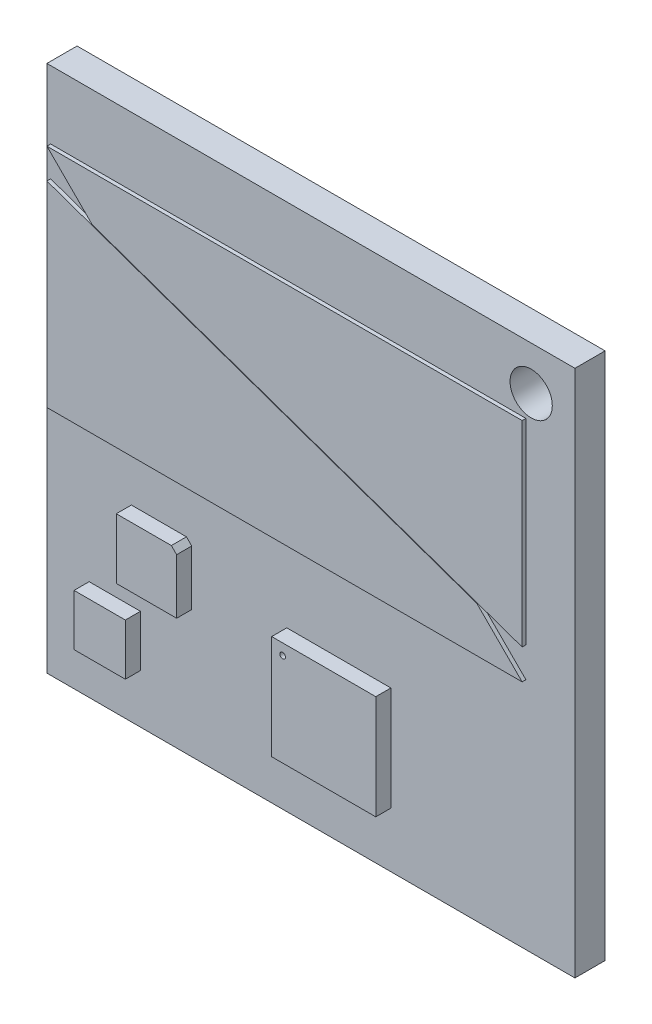
SolidWorks part; units mm, degrees
ref_plane "Front Plane" through (0, 0, 0) normal (0, 0, 1) x (1, 0, 0)
ref_plane "Top Plane" through (0, 0, 0) normal (0, 1, 0) x (1, 0, 0)
ref_plane "Right Plane" through (0, 0, 0) normal (1, 0, 0) x (0, 0, -1)
sketch "Model" plane through (0, 0, 0) normal (0, 0, 1) x (1, 0, 0)
  line L0 (0, 0) -> (35, 0)
  line L1 (35, 0) -> (35, 35)
  line L2 (35, 35) -> (0, 35)
  line L3 (0, 35) -> (0, 0)
  line L4 (22.2, 2.2195) -> (22.2, 2.2805)
  line L5 (18.85, 12.0305) -> (18.85, 11.9695)
  line L6 (24.7805, 2) -> (24.7195, 2)
  line L7 (26.5805, 2) -> (26.5195, 2)
  line L8 (10.7805, 8.85) -> (10.7195, 8.85)
  line L9 (3.9305, 9.25) -> (3.8695, 9.25)
  line L10 (2.6305, 10.35) -> (2.5695, 10.35)
  line L11 (9.35, 4.1305) -> (9.35, 4.0695)
  line L12 (1.8805, 2.7) -> (1.8195, 2.7)
  line L13 (9.9, 1.7305) -> (9.9, 1.6695)
  line L14 (16.47, 0.59) -> (16.47, 1.05)
  line L15 (16.47, 1.51) -> (16.47, 1.05)
  line L16 (16.47, 1.05) -> (16.16, 0.8162)
  line L17 (16.4546, 1.0754) -> (16.16, 1.2684)
  line L18 (29.715, 12.57) -> (30.985, 12.57)
  line L19 (30.985, 12.57) -> (31.62, 11.935)
  line L20 (31.62, 10.665) -> (30.985, 10.03)
  line L21 (31.62, 11.935) -> (32.255, 12.57)
  line L22 (32.255, 12.57) -> (33.525, 12.57)
  line L23 (33.525, 12.57) -> (34.16, 11.935)
  line L24 (34.16, 10.665) -> (33.525, 10.03)
  line L25 (33.525, 10.03) -> (32.255, 10.03)
  line L26 (32.255, 10.03) -> (31.62, 10.665)
  line L27 (29.08, 11.935) -> (29.08, 10.665)
  line L28 (29.715, 12.57) -> (29.08, 11.935)
  line L29 (29.08, 10.665) -> (29.715, 10.03)
  line L30 (30.985, 10.03) -> (29.715, 10.03)
  line L31 (34.16, 11.935) -> (34.16, 10.665)
  line L32 (29.715, 10.02) -> (30.985, 10.02)
  line L33 (30.985, 10.02) -> (31.62, 9.385)
  line L34 (31.62, 8.115) -> (30.985, 7.48)
  line L35 (31.62, 9.385) -> (32.255, 10.02)
  line L36 (32.255, 10.02) -> (33.525, 10.02)
  line L37 (33.525, 10.02) -> (34.16, 9.385)
  line L38 (34.16, 8.115) -> (33.525, 7.48)
  line L39 (33.525, 7.48) -> (32.255, 7.48)
  line L40 (32.255, 7.48) -> (31.62, 8.115)
  line L41 (29.08, 9.385) -> (29.08, 8.115)
  line L42 (29.715, 10.02) -> (29.08, 9.385)
  line L43 (29.08, 8.115) -> (29.715, 7.48)
  line L44 (30.985, 7.48) -> (29.715, 7.48)
  line L45 (34.16, 9.385) -> (34.16, 8.115)
  line L46 (0.25, 15.5) -> (0.25, 28.5)
  line L47 (0.25, 28.5) -> (28.75, 18.5)
  line L48 (0.25, 15.5) -> (31.75, 15.5)
  line L49 (28.75, 18.5) -> (31.75, 15.5)
  line L50 (0.25, 30.5) -> (31.75, 30.5)
  line L51 (31.75, 30.5) -> (31.75, 17.5)
  line L52 (3.25, 27.5) -> (31.75, 17.5)
  line L53 (0.25, 30.5) -> (3.25, 27.5)
  line L54 (15.9, 10.55) -> (22.8, 10.55)
  line L55 (15.9, 10.55) -> (15.9, 3.65)
  line L56 (15.9, 3.65) -> (22.8, 3.65)
  line L57 (22.8, 3.65) -> (22.8, 10.55)
  line L58 (2.8, 6.65) -> (3.4, 6.65)
  line L59 (2.8, 6.65) -> (2.8, 6.05)
  line L60 (2.8, 3.85) -> (2.8, 3.25)
  line L61 (2.8, 3.25) -> (3.4, 3.25)
  line L62 (5.6, 3.25) -> (6.2, 3.25)
  line L63 (6.2, 3.25) -> (6.2, 3.85)
  line L64 (6.135, 6.23) -> (5.76, 6.585)
  line L65 (5.6, 8.8) -> (5.6, 8.45)
  line L66 (5.95, 8.45) -> (5.6, 8.45)
  line L67 (5.6, 12.1) -> (5.6, 12.45)
  line L68 (5.6, 12.45) -> (5.95, 12.45)
  line L69 (9.25, 8.45) -> (9.6, 8.45)
  line L70 (9.6, 8.45) -> (9.6, 8.8)
  line L71 (9.6, 12.1) -> (9.25, 12.45)
  line L72 (18.05, 2.45) -> (18.45, 2.45)
  line L73 (18.45, 2.45) -> (20.05, 2.45)
  line L74 (20.05, 2.45) -> (20.05, 0.85)
  line L75 (20.05, 0.85) -> (18.05, 0.85)
  line L76 (18.05, 0.85) -> (18.05, 2.05)
  line L77 (18.05, 2.05) -> (18.05, 2.45)
  line L78 (18.05, 2.05) -> (18.45, 2.45)
  line L79 (2.8, 3.25) -> (2.8, 6.65)
  line L80 (2.8, 3.25) -> (6.2, 3.25)
  line L81 (2.8, 6.65) -> (6.2, 6.65)
  line L82 (6.2, 3.25) -> (6.2, 6.65)
  line L83 (9.6, 8.45) -> (5.6, 8.45)
  line L84 (9.6, 8.45) -> (9.6, 12.45)
  line L85 (5.6, 8.45) -> (5.6, 12.45)
  line L86 (9.6, 12.45) -> (5.6, 12.45)
  circle A0 centre (32.1, 32.1) radius 1.4
  arc A1 (22.3397, 2.2805) -> (22.0603, 2.2805) centre (22.2, 2.2805) ccw
  arc A2 (22.0603, 2.2195) -> (22.3397, 2.2195) centre (22.2, 2.2195) ccw
  arc A3 (18.7103, 11.9695) -> (18.9897, 11.9695) centre (18.85, 11.9695) ccw
  arc A4 (18.9897, 12.0305) -> (18.7103, 12.0305) centre (18.85, 12.0305) ccw
  arc A5 (24.7195, 2.1397) -> (24.7195, 1.8603) centre (24.7195, 2) ccw
  arc A6 (24.7805, 1.8603) -> (24.7805, 2.1397) centre (24.7805, 2) ccw
  arc A7 (26.5195, 2.1397) -> (26.5195, 1.8603) centre (26.5195, 2) ccw
  arc A8 (26.5805, 1.8603) -> (26.5805, 2.1397) centre (26.5805, 2) ccw
  arc A9 (10.7195, 8.9897) -> (10.7195, 8.7103) centre (10.7195, 8.85) ccw
  arc A10 (10.7805, 8.7103) -> (10.7805, 8.9897) centre (10.7805, 8.85) ccw
  arc A11 (3.8695, 9.3897) -> (3.8695, 9.1103) centre (3.8695, 9.25) ccw
  arc A12 (3.9305, 9.1103) -> (3.9305, 9.3897) centre (3.9305, 9.25) ccw
  arc A13 (2.5695, 10.4897) -> (2.5695, 10.2103) centre (2.5695, 10.35) ccw
  arc A14 (2.6305, 10.2103) -> (2.6305, 10.4897) centre (2.6305, 10.35) ccw
  arc A15 (9.2103, 4.0695) -> (9.4897, 4.0695) centre (9.35, 4.0695) ccw
  arc A16 (9.4897, 4.1305) -> (9.2103, 4.1305) centre (9.35, 4.1305) ccw
  arc A17 (1.8195, 2.8397) -> (1.8195, 2.5603) centre (1.8195, 2.7) ccw
  arc A18 (1.8805, 2.5603) -> (1.8805, 2.8397) centre (1.8805, 2.7) ccw
  arc A19 (9.7603, 1.6695) -> (10.0397, 1.6695) centre (9.9, 1.6695) ccw
  arc A20 (10.0397, 1.7305) -> (9.7603, 1.7305) centre (9.9, 1.7305) ccw
  arc A21 (16.5208, 1.05) -> (16.4192, 1.05) centre (16.47, 1.05) ccw
  arc A22 (16.4192, 0.59) -> (16.5208, 0.59) centre (16.47, 0.59) ccw
  arc A23 (16.4192, 1.05) -> (16.5208, 1.05) centre (16.47, 1.05) ccw
  arc A24 (16.5208, 1.51) -> (16.4192, 1.51) centre (16.47, 1.51) ccw
  arc A25 (16.1294, 0.8568) -> (16.1906, 0.7756) centre (16.16, 0.8162) ccw
  arc A26 (16.5006, 1.0094) -> (16.4394, 1.0906) centre (16.47, 1.05) ccw
  arc A27 (16.1878, 1.3109) -> (16.1322, 1.2259) centre (16.16, 1.2684) ccw
  arc A28 (16.4268, 1.0329) -> (16.4824, 1.1179) centre (16.4546, 1.0754) ccw
  arc A29 (30.985, 12.5192) -> (30.985, 12.6208) centre (30.985, 12.57) ccw
  arc A30 (29.715, 12.6208) -> (29.715, 12.5192) centre (29.715, 12.57) ccw
  arc A31 (31.5841, 11.8991) -> (31.6559, 11.9709) centre (31.62, 11.935) ccw
  arc A32 (31.0209, 12.6059) -> (30.9491, 12.5341) centre (30.985, 12.57) ccw
  arc A33 (30.9491, 10.0659) -> (31.0209, 9.9941) centre (30.985, 10.03) ccw
  arc A34 (31.6559, 10.6291) -> (31.5841, 10.7009) centre (31.62, 10.665) ccw
  arc A35 (32.2909, 12.5341) -> (32.2191, 12.6059) centre (32.255, 12.57) ccw
  arc A36 (31.5841, 11.9709) -> (31.6559, 11.8991) centre (31.62, 11.935) ccw
  arc A37 (33.525, 12.5192) -> (33.525, 12.6208) centre (33.525, 12.57) ccw
  arc A38 (32.255, 12.6208) -> (32.255, 12.5192) centre (32.255, 12.57) ccw
  arc A39 (34.1241, 11.8991) -> (34.1959, 11.9709) centre (34.16, 11.935) ccw
  arc A40 (33.5609, 12.6059) -> (33.4891, 12.5341) centre (33.525, 12.57) ccw
  arc A41 (33.4891, 10.0659) -> (33.5609, 9.9941) centre (33.525, 10.03) ccw
  arc A42 (34.1959, 10.6291) -> (34.1241, 10.7009) centre (34.16, 10.665) ccw
  arc A43 (32.255, 10.0808) -> (32.255, 9.9792) centre (32.255, 10.03) ccw
  arc A44 (33.525, 9.9792) -> (33.525, 10.0808) centre (33.525, 10.03) ccw
  arc A45 (31.6559, 10.7009) -> (31.5841, 10.6291) centre (31.62, 10.665) ccw
  arc A46 (32.2191, 9.9941) -> (32.2909, 10.0659) centre (32.255, 10.03) ccw
  arc A47 (29.0292, 10.665) -> (29.1308, 10.665) centre (29.08, 10.665) ccw
  arc A48 (29.1308, 11.935) -> (29.0292, 11.935) centre (29.08, 11.935) ccw
  arc A49 (29.0441, 11.9709) -> (29.1159, 11.8991) centre (29.08, 11.935) ccw
  arc A50 (29.7509, 12.5341) -> (29.6791, 12.6059) centre (29.715, 12.57) ccw
  arc A51 (29.6791, 9.9941) -> (29.7509, 10.0659) centre (29.715, 10.03) ccw
  arc A52 (29.1159, 10.7009) -> (29.0441, 10.6291) centre (29.08, 10.665) ccw
  arc A53 (29.715, 10.0808) -> (29.715, 9.9792) centre (29.715, 10.03) ccw
  arc A54 (30.985, 9.9792) -> (30.985, 10.0808) centre (30.985, 10.03) ccw
  arc A55 (34.1092, 10.665) -> (34.2108, 10.665) centre (34.16, 10.665) ccw
  arc A56 (34.2108, 11.935) -> (34.1092, 11.935) centre (34.16, 11.935) ccw
  arc A57 (30.985, 9.9692) -> (30.985, 10.0708) centre (30.985, 10.02) ccw
  arc A58 (29.715, 10.0708) -> (29.715, 9.9692) centre (29.715, 10.02) ccw
  arc A59 (31.5841, 9.3491) -> (31.6559, 9.4209) centre (31.62, 9.385) ccw
  arc A60 (31.0209, 10.0559) -> (30.9491, 9.9841) centre (30.985, 10.02) ccw
  arc A61 (30.9491, 7.5159) -> (31.0209, 7.4441) centre (30.985, 7.48) ccw
  arc A62 (31.6559, 8.0791) -> (31.5841, 8.1509) centre (31.62, 8.115) ccw
  arc A63 (32.2909, 9.9841) -> (32.2191, 10.0559) centre (32.255, 10.02) ccw
  arc A64 (31.5841, 9.4209) -> (31.6559, 9.3491) centre (31.62, 9.385) ccw
  arc A65 (33.525, 9.9692) -> (33.525, 10.0708) centre (33.525, 10.02) ccw
  arc A66 (32.255, 10.0708) -> (32.255, 9.9692) centre (32.255, 10.02) ccw
  arc A67 (34.1241, 9.3491) -> (34.1959, 9.4209) centre (34.16, 9.385) ccw
  arc A68 (33.5609, 10.0559) -> (33.4891, 9.9841) centre (33.525, 10.02) ccw
  arc A69 (33.4891, 7.5159) -> (33.5609, 7.4441) centre (33.525, 7.48) ccw
  arc A70 (34.1959, 8.0791) -> (34.1241, 8.1509) centre (34.16, 8.115) ccw
  arc A71 (32.255, 7.5308) -> (32.255, 7.4292) centre (32.255, 7.48) ccw
  arc A72 (33.525, 7.4292) -> (33.525, 7.5308) centre (33.525, 7.48) ccw
  arc A73 (31.6559, 8.1509) -> (31.5841, 8.0791) centre (31.62, 8.115) ccw
  arc A74 (32.2191, 7.4441) -> (32.2909, 7.5159) centre (32.255, 7.48) ccw
  arc A75 (29.0292, 8.115) -> (29.1308, 8.115) centre (29.08, 8.115) ccw
  arc A76 (29.1308, 9.385) -> (29.0292, 9.385) centre (29.08, 9.385) ccw
  arc A77 (29.0441, 9.4209) -> (29.1159, 9.3491) centre (29.08, 9.385) ccw
  arc A78 (29.7509, 9.9841) -> (29.6791, 10.0559) centre (29.715, 10.02) ccw
  arc A79 (29.6791, 7.4441) -> (29.7509, 7.5159) centre (29.715, 7.48) ccw
  arc A80 (29.1159, 8.1509) -> (29.0441, 8.0791) centre (29.08, 8.115) ccw
  arc A81 (29.715, 7.5308) -> (29.715, 7.4292) centre (29.715, 7.48) ccw
  arc A82 (30.985, 7.4292) -> (30.985, 7.5308) centre (30.985, 7.48) ccw
  arc A83 (34.1092, 8.115) -> (34.2108, 8.115) centre (34.16, 8.115) ccw
  arc A84 (34.2108, 9.385) -> (34.1092, 9.385) centre (34.16, 9.385) ccw
  arc A85 (0.2818, 28.5) -> (0.2182, 28.5) centre (0.25, 28.5) ccw
  arc A86 (0.2182, 15.5) -> (0.2818, 15.5) centre (0.25, 15.5) ccw
  arc A87 (28.7395, 18.47) -> (28.7605, 18.53) centre (28.75, 18.5) ccw
  arc A88 (0.2605, 28.53) -> (0.2395, 28.47) centre (0.25, 28.5) ccw
  arc A89 (31.75, 15.4682) -> (31.75, 15.5318) centre (31.75, 15.5) ccw
  arc A90 (0.25, 15.5318) -> (0.25, 15.4682) centre (0.25, 15.5) ccw
  arc A91 (31.7275, 15.4775) -> (31.7725, 15.5225) centre (31.75, 15.5) ccw
  arc A92 (28.7725, 18.5225) -> (28.7275, 18.4775) centre (28.75, 18.5) ccw
  arc A93 (31.75, 30.4683) -> (31.75, 30.5317) centre (31.75, 30.5) ccw
  arc A94 (0.25, 30.5317) -> (0.25, 30.4683) centre (0.25, 30.5) ccw
  arc A95 (31.7183, 17.5) -> (31.7817, 17.5) centre (31.75, 17.5) ccw
  arc A96 (31.7817, 30.5) -> (31.7183, 30.5) centre (31.75, 30.5) ccw
  arc A97 (31.7395, 17.47) -> (31.7605, 17.53) centre (31.75, 17.5) ccw
  arc A98 (3.2605, 27.53) -> (3.2395, 27.47) centre (3.25, 27.5) ccw
  arc A99 (3.2275, 27.4775) -> (3.2725, 27.5225) centre (3.25, 27.5) ccw
  arc A100 (0.2725, 30.5225) -> (0.2275, 30.4775) centre (0.25, 30.5) ccw
  arc A101 (22.8, 10.5183) -> (22.8, 10.5818) centre (22.8, 10.55) ccw
  arc A102 (15.9, 10.5818) -> (15.9, 10.5183) centre (15.9, 10.55) ccw
  arc A103 (15.8682, 3.65) -> (15.9318, 3.65) centre (15.9, 3.65) ccw
  arc A104 (15.9318, 10.55) -> (15.8682, 10.55) centre (15.9, 10.55) ccw
  arc A105 (22.8, 3.6183) -> (22.8, 3.6818) centre (22.8, 3.6501) ccw
  arc A106 (15.9, 3.6818) -> (15.9, 3.6183) centre (15.9, 3.6501) ccw
  arc A107 (22.8317, 10.55) -> (22.7683, 10.55) centre (22.8, 10.55) ccw
  arc A108 (22.7683, 3.65) -> (22.8317, 3.65) centre (22.8, 3.65) ccw
  circle A109 centre (16.63, 9.82) radius 0.1855
  arc A110 (3.4, 6.5992) -> (3.4, 6.7008) centre (3.4, 6.65) ccw
  arc A111 (2.8, 6.7008) -> (2.8, 6.5992) centre (2.8, 6.65) ccw
  arc A112 (2.7492, 6.05) -> (2.8508, 6.05) centre (2.8, 6.05) ccw
  arc A113 (2.8508, 6.65) -> (2.7492, 6.65) centre (2.8, 6.65) ccw
  arc A114 (2.7492, 3.25) -> (2.8508, 3.25) centre (2.8, 3.25) ccw
  arc A115 (2.8508, 3.85) -> (2.7492, 3.85) centre (2.8, 3.85) ccw
  arc A116 (3.4, 3.1992) -> (3.4, 3.3008) centre (3.4, 3.25) ccw
  arc A117 (2.8, 3.3008) -> (2.8, 3.1992) centre (2.8, 3.25) ccw
  arc A118 (6.2, 3.1992) -> (6.2, 3.3008) centre (6.2, 3.25) ccw
  arc A119 (5.6, 3.3008) -> (5.6, 3.1992) centre (5.6, 3.25) ccw
  arc A120 (6.2508, 3.85) -> (6.1492, 3.85) centre (6.2, 3.85) ccw
  arc A121 (6.1492, 3.25) -> (6.2508, 3.25) centre (6.2, 3.25) ccw
  arc A122 (5.7949, 6.6219) -> (5.7251, 6.5481) centre (5.76, 6.585) ccw
  arc A123 (6.1001, 6.1931) -> (6.1699, 6.2669) centre (6.135, 6.23) ccw
  arc A124 (5.5492, 8.45) -> (5.6508, 8.45) centre (5.6, 8.45) ccw
  arc A125 (5.6508, 8.8) -> (5.5492, 8.8) centre (5.6, 8.8) ccw
  arc A126 (5.6, 8.5008) -> (5.6, 8.3992) centre (5.6, 8.45) ccw
  arc A127 (5.95, 8.3992) -> (5.95, 8.5008) centre (5.95, 8.45) ccw
  arc A128 (5.6508, 12.45) -> (5.5492, 12.45) centre (5.6, 12.45) ccw
  arc A129 (5.5492, 12.1) -> (5.6508, 12.1) centre (5.6, 12.1) ccw
  arc A130 (5.95, 12.3992) -> (5.95, 12.5008) centre (5.95, 12.45) ccw
  arc A131 (5.6, 12.5008) -> (5.6, 12.3992) centre (5.6, 12.45) ccw
  arc A132 (9.6, 8.3992) -> (9.6, 8.5008) centre (9.6, 8.45) ccw
  arc A133 (9.25, 8.5008) -> (9.25, 8.3992) centre (9.25, 8.45) ccw
  arc A134 (9.6508, 8.8) -> (9.5492, 8.8) centre (9.6, 8.8) ccw
  arc A135 (9.5492, 8.45) -> (9.6508, 8.45) centre (9.6, 8.45) ccw
  arc A136 (9.2859, 12.4859) -> (9.2141, 12.4141) centre (9.25, 12.45) ccw
  arc A137 (9.5641, 12.0641) -> (9.6359, 12.1359) centre (9.6, 12.1) ccw
  arc A138 (18.45, 2.4183) -> (18.45, 2.4818) centre (18.45, 2.45) ccw
  arc A139 (18.05, 2.4818) -> (18.05, 2.4183) centre (18.05, 2.45) ccw
  arc A140 (20.05, 2.4183) -> (20.05, 2.4818) centre (20.05, 2.45) ccw
  arc A141 (18.45, 2.4818) -> (18.45, 2.4183) centre (18.45, 2.45) ccw
  arc A142 (20.0183, 0.85) -> (20.0817, 0.85) centre (20.05, 0.85) ccw
  arc A143 (20.0817, 2.45) -> (20.0183, 2.45) centre (20.05, 2.45) ccw
  arc A144 (18.05, 0.8818) -> (18.05, 0.8183) centre (18.05, 0.85) ccw
  arc A145 (20.05, 0.8183) -> (20.05, 0.8818) centre (20.05, 0.85) ccw
  arc A146 (18.0817, 2.05) -> (18.0183, 2.05) centre (18.05, 2.05) ccw
  arc A147 (18.0183, 0.85) -> (18.0817, 0.85) centre (18.05, 0.85) ccw
  arc A148 (18.0817, 2.45) -> (18.0183, 2.45) centre (18.05, 2.45) ccw
  arc A149 (18.0183, 2.05) -> (18.0817, 2.05) centre (18.05, 2.05) ccw
  arc A150 (18.4725, 2.4275) -> (18.4275, 2.4725) centre (18.45, 2.45) ccw
  arc A151 (18.0275, 2.0725) -> (18.0725, 2.0275) centre (18.05, 2.05) ccw
  point P405 (32.45, 5.1)
  point P406 (29.8, 2.45)
  point P407 (22.2, 2.25)
  point P408 (12.45, 4.1)
  point P409 (12.45, 5.4)
  point P410 (18.85, 12)
  point P411 (24.75, 2)
  point P412 (26.55, 2)
  point P413 (10.75, 8.85)
  point P414 (3.9, 9.25)
  point P415 (2.6, 10.35)
  point P416 (9.35, 4.1)
  point P417 (1.85, 2.7)
  point P418 (9.9, 1.7)
  point P419 (16.3, 1.05)
  point P420 (30.35, 11.3)
  point P421 (30.35, 8.75)
  point P422 (26.25, 7.85)
  point P423 (17.5, 33.5)
  point P424 (33.5, 17.5)
  point P425 (27.5, 11.65)
  point P426 (22.35, 12)
  point P427 (14.2, 11.1)
  point P428 (9.35, 5.4)
  point P429 (14.7, 2.3)
  point P430 (33.55, 20.725)
  point P431 (16, 23)
  point P432 (19.35, 7.1)
  point P433 (4.5, 4.95)
  point P434 (7.6, 10.45)
  point P435 (19.05, 1.65)
extrude "Boss-Extrude1" add sketch "Model" against normal blind 2 contours L2 L3 L0 L1
extrude "Cut-Extrude1" cut sketch "Model<3>" against normal through all contours A0 region at (32.1, 32.1, 0)
sketch "Model<3>" plane through (0, 0, 0) normal (0, 0, 1) x (1, 0, 0) same geometry as "Model"
extrude "Boss-Extrude2" add sketch "Model<4>" along normal blind 1 contours L56 L57 L54 L55 A109 | L63 L82 L81 L58 L59 L79 L60 L61 L80 L62 | L71 L86 L68 L85 L67 L65 L83 L66 L69 L70 L84 region at (19.3562, 7.0938, 0) region at (4.5, 4.95, 0) region at (7.5928, 10.4428, 0)
sketch "Model<4>" plane through (0, 0, 0) normal (0, 0, 1) x (1, 0, 0) same geometry as "Model"
extrude "Boss-Extrude3" add sketch "Model<5>" along normal blind 0.25 contours L50 L53 L52 L51 | L49 L47 L46 L48 region at (11.8839, 19.9527, 0) region at (20.1161, 26.0473, 0)
sketch "Model<5>" plane through (0, 0, 0) normal (0, 0, 1) x (1, 0, 0) same geometry as "Model"
